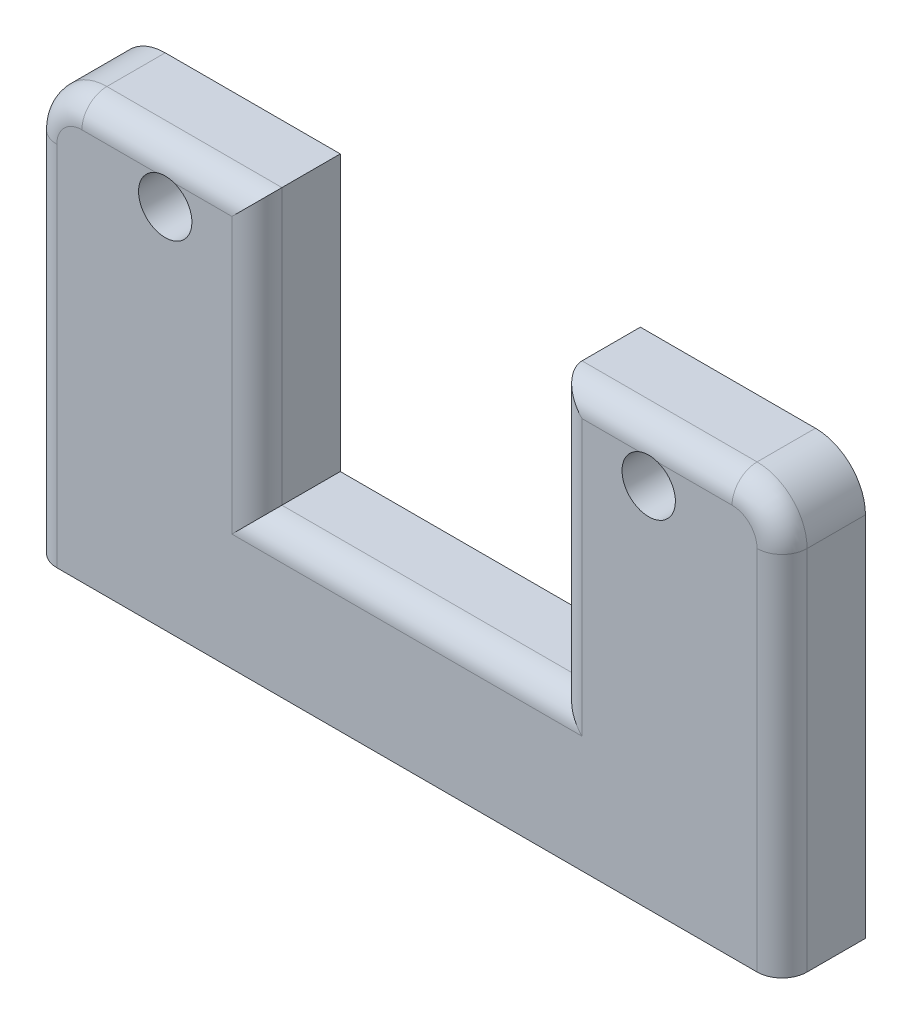
SolidWorks part; units mm, degrees
ref_plane "前视基准面" through (0, 0, 0) normal (0, 0, 1) x (1, 0, 0)
ref_plane "上视基准面" through (0, 0, 0) normal (0, 1, 0) x (1, 0, 0)
ref_plane "右视基准面" through (0, 0, 0) normal (1, 0, 0) x (0, 0, -1)
sketch "Model" plane through (0, 0, 0) normal (0, 0, 1) x (1, 0, 0)
  line L2 (241.1199, 237.0959) -> (251.6199, 237.0959)
  line L3 (251.6199, 237.0959) -> (251.6199, 220.5959)
  line L4 (269.6199, 237.0959) -> (269.6199, 220.5959)
  line L5 (251.6199, 220.5959) -> (269.6199, 220.5959)
  line L6 (238.1199, 212.0959) -> (283.1199, 212.0959)
  line L7 (238.1199, 212.0959) -> (238.1199, 234.0959)
  line L8 (280.1199, 237.0959) -> (269.6199, 237.0959)
  line L9 (283.1199, 212.0959) -> (283.1199, 234.0959)
  circle A0 centre (246.1199, 234.0959) radius 1.6
  circle A1 centre (275.1199, 234.0959) radius 1.6
  arc A2 (241.1199, 237.0959) -> (238.1199, 234.0959) centre (241.1199, 234.0959) ccw
  arc A3 (283.1199, 234.0959) -> (280.1199, 237.0959) centre (280.1199, 234.0959) ccw
extrude "凸台-拉伸1" add sketch "Model" along normal blind 5
sketch "草图2" plane through (0, 212.0959, 0) normal (0, -1, 0) x (1, 0, 0)
  line L1 (260.6199, 5) -> (260.6199, 0) construction
  line L2 (238.1199, 5) -> (283.1199, 5) construction
  line L3 (238.1199, 0) -> (283.1199, 0) construction
  circle A0 centre (241.3699, 2.5) radius 1.25
  circle A1 centre (279.8699, 2.5) radius 1.25
  dimension "D2" = 2.5
  dimension "D3" = 2.5
  dimension "D4" = 38.5
  dimension "D1" = 19.25
extrude "切除-拉伸1" cut sketch "草图2" against normal blind 6
fillet "圆角1" radius 1.5 9 edges at (274.8699, 237.0959, 5) (282.2412, 236.2172, 5) (246.3699, 237.0959, 5) (238.9986, 236.2172, 5) (269.6199, 228.8459, 5) (260.6199, 220.5959, 5) (251.6199, 228.8459, 5) (283.1199, 223.0959, 5) (238.1199, 223.0959, 5)
